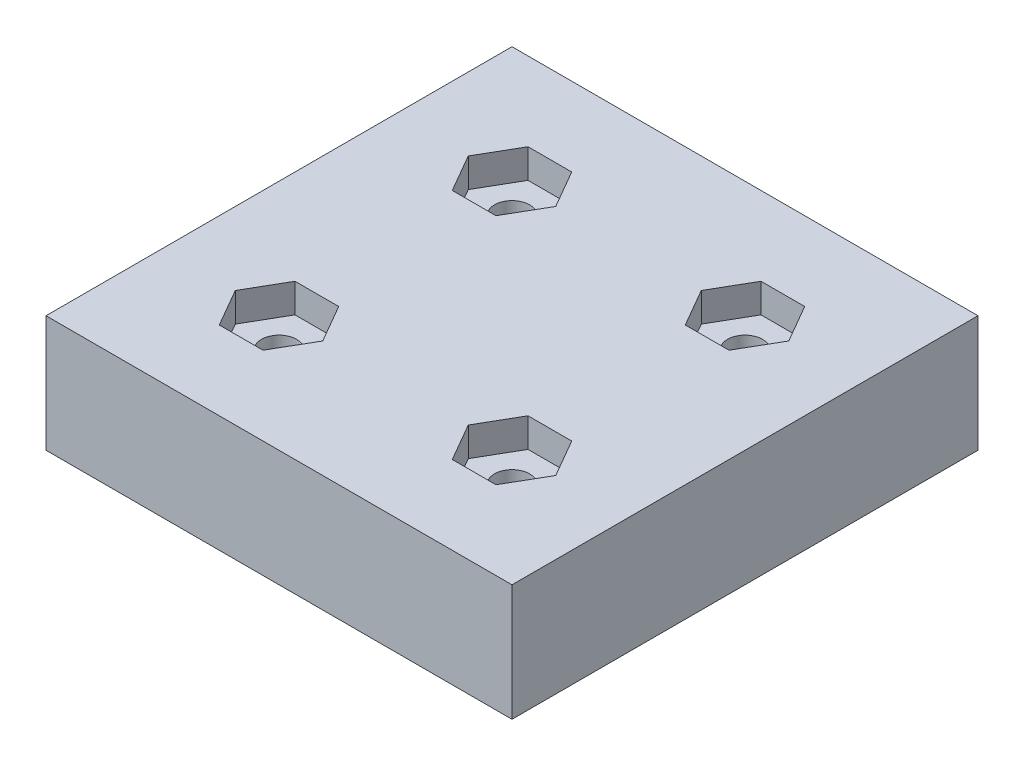
SolidWorks part; units mm, degrees
ref_plane "Front Plane" through (0, 0, 0) normal (0, 0, 1) x (1, 0, 0)
ref_plane "Top Plane" through (0, 0, 0) normal (0, 1, 0) x (1, 0, 0)
ref_plane "Right Plane" through (0, 0, 0) normal (1, 0, 0) x (0, 0, -1)
sketch "Sketch1" plane through (0, 0, 0) normal (0, 1, 0) x (1, 0, 0)
  line L1 (0, 0) -> (40, 0)
  line L2 (0, 0) -> (0, 40)
  line L3 (0, 40) -> (40, 40)
  line L4 (40, 0) -> (40, 40)
  circle A0 centre (10, 30) radius 1.5
  circle A1 centre (30, 30) radius 1.5
  circle A2 centre (30, 10) radius 1.5
  circle A3 centre (10, 10) radius 1.5
  dimension "D11" = 3
  dimension "D12" = 3
  dimension "D13" = 3
  dimension "D14" = 3
  dimension "D1" = 40
  dimension "D2" = 40
  dimension "D3" = 10
  dimension "D4" = 10
  dimension "D5" = 10
  dimension "D6" = 10
  dimension "D7" = 10
  dimension "D8" = 10
  dimension "D9" = 10
  dimension "D10" = 10
extrude "Boss-Extrude1" add sketch "Sketch1" along normal blind 10
sketch "Sketch2" plane through (0, 10, 0) normal (0, 1, 0) x (1, 0, 0)
  line L0 (10, 10) -> (30, 10) construction
  line L1 (30, 10) -> (30, 30) construction
  line L2 (30, 30) -> (10, 30) construction
  line L3 (10, 30) -> (10, 10) construction
  line L5 (13.7528, 10) -> (11.8764, 13.25)
  line L6 (11.8764, 13.25) -> (8.1236, 13.25)
  line L7 (8.1236, 13.25) -> (6.2472, 10)
  line L8 (6.2472, 10) -> (8.1236, 6.75)
  line L9 (8.1236, 6.75) -> (11.8764, 6.75)
  line L10 (11.8764, 6.75) -> (13.7528, 10)
  line L11 (26.2472, 10) -> (28.1236, 6.75)
  line L12 (28.1236, 6.75) -> (31.8764, 6.75)
  line L13 (31.8764, 6.75) -> (33.7528, 10)
  line L14 (33.7528, 10) -> (31.8764, 13.25)
  line L15 (31.8764, 13.25) -> (28.1236, 13.25)
  line L16 (28.1236, 13.25) -> (26.2472, 10)
  line L17 (26.2472, 30) -> (28.1236, 26.75)
  line L18 (28.1236, 26.75) -> (31.8764, 26.75)
  line L19 (31.8764, 26.75) -> (33.7528, 30)
  line L20 (33.7528, 30) -> (31.8764, 33.25)
  line L21 (31.8764, 33.25) -> (28.1236, 33.25)
  line L22 (28.1236, 33.25) -> (26.2472, 30)
  line L23 (13.7528, 30) -> (11.8764, 33.25)
  line L24 (11.8764, 33.25) -> (8.1236, 33.25)
  line L25 (8.1236, 33.25) -> (6.2472, 30)
  line L26 (6.2472, 30) -> (8.1236, 26.75)
  line L27 (8.1236, 26.75) -> (11.8764, 26.75)
  line L28 (11.8764, 26.75) -> (13.7528, 30)
  circle A0 centre (10, 10) radius 3.25 construction
  circle A1 centre (30, 10) radius 3.25 construction
  circle A2 centre (30, 30) radius 3.25 construction
  circle A3 centre (10, 30) radius 3.25 construction
  dimension "D1" = 6.5
  dimension "D2" = 6.5
  dimension "D3" = 6.5
  dimension "D4" = 6.5
extrude "Cut-Extrude1" cut sketch "Sketch2" against normal blind 2.5
equation "\"hSpacing\"=10"
equation "\"D3@Sketch1\"=\"hSpacing\""
equation "\"D5@Sketch1\"=\"hSpacing\""
equation "\"D6@Sketch1\"=\"hSpacing\""
equation "\"D4@Sketch1\"=\"hSpacing\""
equation "\"D7@Sketch1\"=\"hSpacing\""
equation "\"D8@Sketch1\"=\"hSpacing\""
equation "\"D9@Sketch1\"=\"hSpacing\""
equation "\"D10@Sketch1\"=\"hSpacing\""
equation "\"hDiam\"=3"
equation "\"D11@Sketch1\"=\"hDiam\""
equation "\"D12@Sketch1\"=\"hDiam\""
equation "\"D13@Sketch1\"=\"hDiam\""
equation "\"D14@Sketch1\"=\"hDiam\""
equation "\"nutFlat\"=6.5"
equation "\"D1@Sketch2\"=\"nutFlat\""
equation "\"D2@Sketch2\"=\"nutFlat\""
equation "\"D3@Sketch2\"=\"nutFlat\""
equation "\"D4@Sketch2\"=\"nutFlat\""
